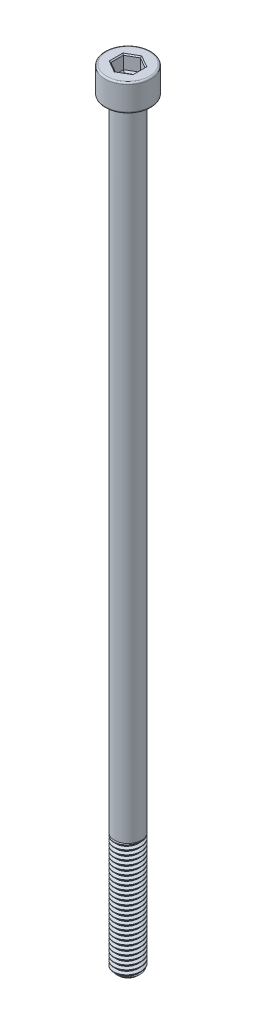
SolidWorks part; units mm, degrees
material "AISI Type A2 Tool Steel"
ref_plane "Front Plane" through (0, 0, 0) normal (0, 0, 1) x (1, 0, 0)
ref_plane "Top Plane" through (0, 0, 0) normal (0, 1, 0) x (1, 0, 0)
ref_plane "Right Plane" through (0, 0, 0) normal (1, 0, 0) x (0, 0, -1)
sketch "Sketch1" plane through (0, 0, 0) normal (0, 1, 0) x (1, 0, 0)
  circle A0 centre (0, 0) radius 2.5
  dimension "D1" = 5
extrude "Boss-Extrude1" add sketch "Sketch1" along normal blind 22
thread "Thread1" pitch 0.8 start angle 0, offset 1, length 0, pitch 0.8, diameter 5
ref_plane "Plane1" through (-2.5, 23, 0) normal (0, 0, 1) x (-1, 0, 0)
sketch "Thread Profile1" plane through (-2.5, 23, 0) normal (0, 0, 1) x (-1, 0, 0)
  line L0 (0, 0) -> (0, 0.8) construction
  line L11 (0, 0) -> (0, 0.7)
  line L12 (0, 0.7) -> (-0.433, 0.45)
  line L13 (-0.433, 0.45) -> (-0.433, 0.25)
  line L15 (-0.433, 0.25) -> (0, 0)
  line L17 (-0.433, 0.35) -> (0, 0.35) construction
  point P2 (0, 0)
  dimension "Pitch" = 0.8
  dimension "Profile_Angle" = 60
  dimension "Profile_Land" = 0.2
  dimension "Profile_Height" = 0.433
sketch "Sketch2" plane through (0, 22, 0) normal (0, 1, 0) x (1, 0, 0)
  circle A0 centre (0, 0) radius 2.5
  dimension "D1" = 5
extrude "Boss-Extrude2" add sketch "Sketch2" along normal blind 118
sketch "Sketch3" plane through (0, 140, 0) normal (0, 1, 0) x (1, 0, 0)
  circle A0 centre (0, 0) radius 4.25
  dimension "D1" = 8.5
extrude "Boss-Extrude3" add sketch "Sketch3" along normal blind 5
fillet "Fillet1" radius 0.3 2 edges at (0, 140, 4.25) (0, 145, 4.25)
sketch "Sketch4" plane through (0, 0, 0) normal (0, 0, 1) x (1, 0, 0)
  line L0 (0, 0) -> (0, 0.4416) construction
  line L1 (0, 0) -> (2.51, 0) construction
  line L2 (2.51, 0) -> (2.51, 0.7)
  line L3 (2.51, 0.7) -> (1.81, 0)
  line L4 (1.81, 0) -> (2.51, 0)
  dimension "D1" = 0.7
  dimension "D2" = 45
  dimension "D3" = 2.51
revolve "Cut-Revolve1" cut sketch "Sketch4" angle 360 about L0
sketch "Sketch5" plane through (0, 145, 0) normal (0, 1, 0) x (1, 0, 0)
  line L1 (0, 2.3094) -> (-2, 1.1547)
  line L2 (-2, 1.1547) -> (-2, -1.1547)
  line L3 (-2, -1.1547) -> (0, -2.3094)
  line L4 (0, -2.3094) -> (2, -1.1547)
  line L5 (2, -1.1547) -> (2, 1.1547)
  line L6 (2, 1.1547) -> (0, 2.3094)
  circle A0 centre (0, 0) radius 2 construction
  dimension "D1" = 4
extrude "Cut-Extrude1" cut sketch "Sketch5" against normal blind 2.5
chamfer "Chamfer1" distance 0.2 angle 45 6 edges at (-1, 145, 1.7321) (1, 145, 1.7321) (2, 145, 0) (1, 145, -1.7321) (-1, 145, -1.7321) (-2, 145, 0)
sketch "Sketch6" plane through (0, 142.5, 0) normal (0, 1, 0) x (1, 0, 0)
  line L1 (0, 2.3094) -> (-2, 1.1547)
  line L2 (-2, 1.1547) -> (-2, -1.1547)
  line L3 (-2, -1.1547) -> (0, -2.3094)
  line L4 (0, -2.3094) -> (2, -1.1547)
  line L5 (2, -1.1547) -> (2, 1.1547)
  line L6 (2, 1.1547) -> (0, 2.3094)
  circle A0 centre (0, 0) radius 2 construction
extrude "Cut-Extrude2" cut sketch "Sketch6" against normal blind 0.3 draft 45
